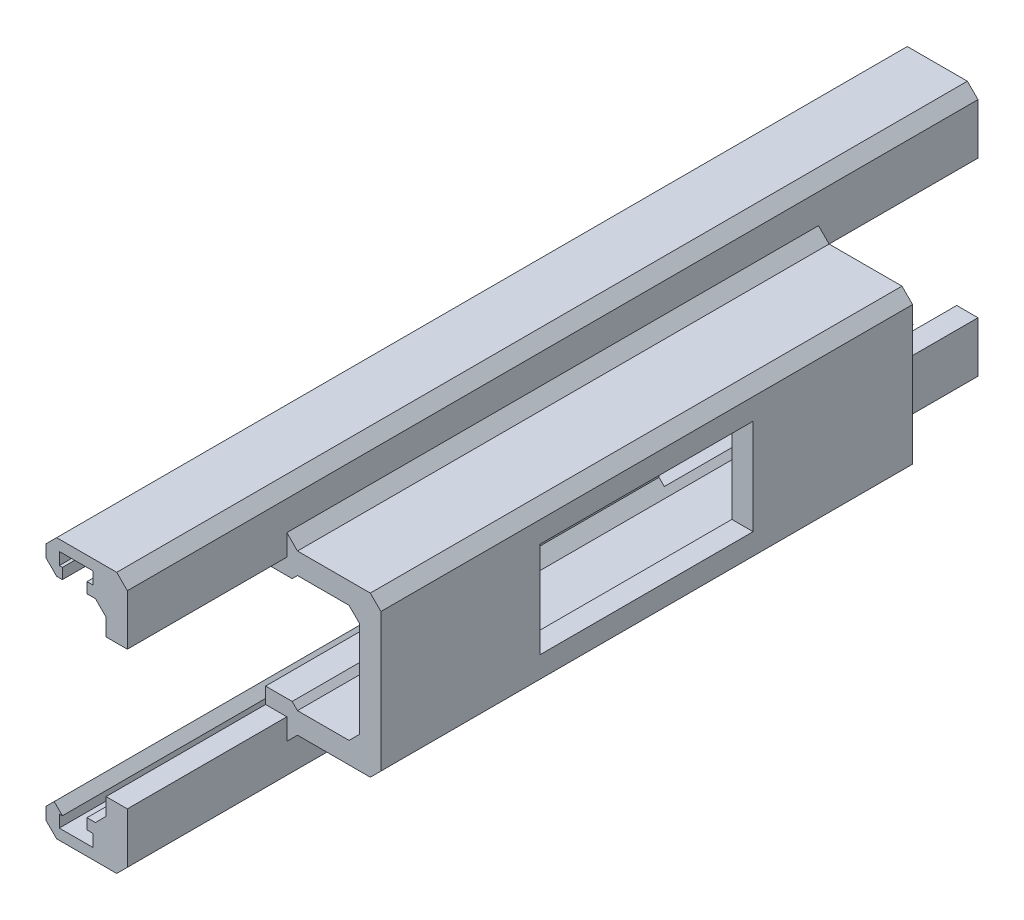
SolidWorks part; units mm, degrees
ref_plane "Plan de face" through (0, 0, 0) normal (0, 0, 1) x (1, 0, 0)
ref_plane "Plan de dessus" through (0, 0, 0) normal (0, 1, 0) x (1, 0, 0)
ref_plane "Plan de droite" through (0, 0, 0) normal (1, 0, 0) x (0, 0, -1)
sketch "Esquisse1" plane through (0, 0, 0) normal (0, 0, 1) x (1, 0, 0)
  line L0 (0, 1.9005) -> (0, -0.7738) construction
  line L2 (-2.5615, 1.0788) -> (-2.5615, -0.9212)
  line L3 (-1.9625, -2.4324) -> (-0.2921, -2.4324) construction
  line L4 (2.0615, 1.0788) -> (2.0615, -0.9212)
  line L5 (0.1295, 1.0788) -> (-0.2921, -2.4324) construction
  line L6 (-1.9625, -2.4324) -> (0.8705, 1.0788) construction
  line L7 (-3.15, -3.2212) -> (3.15, -3.2212)
  line L8 (-3.15, -3.2212) -> (-3.15, -0.9212)
  line L9 (-3.15, -0.9212) -> (-2.5615, -0.9212)
  line L10 (3.15, -3.2212) -> (3.15, -0.9212)
  line L11 (-3.15, -0.9212) -> (3.15, -3.2212) construction
  line L12 (2.0615, -0.9212) -> (3.15, -0.9212)
  line L13 (3.15, -0.9212) -> (-3.15, -3.2212) construction
  line L14 (0.1295, 1.0788) -> (0.8705, 1.0788) construction
  line L15 (-5.65, 1.0788) -> (-2.5615, 1.0788)
  line L16 (-5.65, 1.0788) -> (-5.65, -5.2212)
  line L17 (-5.65, -5.2212) -> (5.65, -5.2212)
  line L19 (-5.65, 1.0788) -> (5.65, -5.2212) construction
  line L20 (-5.65, -5.2212) -> (5.65, 1.0788) construction
  line L21 (2.0615, 1.0788) -> (5.65, 1.0788)
  line L22 (0, -0.2112) -> (0, 38.8288) construction
  line L23 (0, 19.3088) -> (-5.65, 19.3088) construction
  line L24 (-5.65, 43.8388) -> (5.65, 37.5388) construction
  line L25 (-5.65, 37.5388) -> (5.65, 43.8388) construction
  line L26 (3.15, 39.5388) -> (-3.15, 41.8388) construction
  line L27 (-3.15, 39.5388) -> (3.15, 41.8388) construction
  line L28 (-1.9625, 41.0501) -> (0.8705, 37.5388) construction
  line L29 (0.1295, 37.5388) -> (-0.2921, 41.0501) construction
  line L30 (0, 36.7172) -> (0, 39.3915) construction
  line L31 (2.0615, 37.5388) -> (5.65, 37.5388)
  line L33 (-5.65, 43.8388) -> (5.65, 43.8388)
  line L34 (-5.65, 37.5388) -> (-5.65, 43.8388)
  line L35 (-5.65, 37.5388) -> (-2.5615, 37.5388)
  line L36 (0.1295, 37.5388) -> (0.8705, 37.5388)
  line L37 (2.0615, 39.5388) -> (3.15, 39.5388)
  line L38 (3.15, 41.8388) -> (3.15, 39.5388)
  line L39 (-3.15, 39.5388) -> (-2.5615, 39.5388)
  line L40 (-3.15, 41.8388) -> (-3.15, 39.5388)
  line L41 (-3.15, 41.8388) -> (3.15, 41.8388)
  line L42 (2.0615, 37.5388) -> (2.0615, 39.5388)
  line L43 (-1.9625, 41.0501) -> (-0.2921, 41.0501)
  line L44 (-2.5615, 37.5388) -> (-2.5615, 39.5388)
  line L46 (5.65, 43.8388) -> (9.65, 43.8388)
  line L47 (5.65, 37.5388) -> (5.65, 1.0788)
  line L48 (5.65, -5.2212) -> (9.65, -5.2212)
  line L49 (9.65, 43.8388) -> (9.65, -5.2212)
  line L50 (5.65, -5.2212) -> (9.45, -5.2212)
  line L51 (5.65, 1.0788) -> (5.65, 37.5388)
  line L52 (5.65, 43.8388) -> (9.45, 43.8388)
  point P0 (0, 0)
  point P13 (0, -2.0712)
  point P43 (0, 40.6888)
  point P44 (0, 38.6177)
  dimension "D1" = 6.3
  dimension "D2" = 2.3
  dimension "D3" = 11.3
  dimension "D4" = 6.3
  dimension "D5" = 3.01
  dimension "D6" = 39.04
  dimension "D7" = 4
extrude "Boss.-Extru.1" add sketch "Esquisse1" along normal blind 80 and the other way blind 80 contours L21 L4 L12 L10 L7 L3 L8 L9 L2 L15 L16 L17 region at (-3.0754, 0.0788, 0)
sketch "Esquisse4" plane through (5.65, 0, 0) normal (-1, 0, 0) x (0, 0, 1)
  line L0 (-80, 37.5388) -> (80, 1.0788) construction
  line L1 (80, 37.5388) -> (-80, 1.0788) construction
  line L2 (-52.8674, 19.3088) -> (52.8674, 19.3088) construction
  line L3 (-16.5, 25.4088) -> (16.5, 25.4088) construction
  line L4 (-16.5, 25.4088) -> (-16.5, 13.2088) construction
  line L5 (-16.5, 13.2088) -> (16.5, 13.2088) construction
  line L6 (16.5, 25.4088) -> (16.5, 13.2088) construction
  line L7 (-16.5, 25.4088) -> (16.5, 13.2088) construction
  line L8 (-16.5, 13.2088) -> (16.5, 25.4088) construction
  line L9 (-11.5, 25.4088) -> (11.5, 25.4088)
  line L10 (-11.5, 25.4088) -> (-11.5, 13.2088)
  line L11 (-11.5, 13.2088) -> (11.5, 13.2088)
  line L12 (11.5, 25.4088) -> (11.5, 13.2088)
  line L13 (-11.5, 25.4088) -> (11.5, 13.2088) construction
  line L14 (-11.5, 13.2088) -> (11.5, 25.4088) construction
  line L15 (0, 25.4088) -> (0, 22.1174) construction
  circle A0 centre (-14, 19.3088) radius 1.5
  circle A1 centre (14, 19.3088) radius 1.5
  point P8 (0, 19.3088)
  point P13 (0, 19.3088)
  point P21 (0, 19.3088)
  point P23 (-11.5, 19.3088)
  dimension "D4" = 3
  dimension "D1" = 33
  dimension "D2" = 12.2
  dimension "D3" = 23
  dimension "D5" = 2.5
extrude "Enlèv. mat.-Extru.1" cut sketch "Esquisse4" against normal blind 95
sketch "Esquisse5" plane through (9.65, 0, 0) normal (1, 0, 0) x (0, 0, -1)
  line L0 (16.5, 25.4088) -> (16.5, 13.2088) construction
  line L1 (16.5, 13.2088) -> (-16.5, 13.2088) construction
  line L2 (16.5, 25.4088) -> (-16.5, 25.4088) construction
  line L3 (-16.5, 25.4088) -> (-16.5, 13.2088) construction
  line L4 (16.5, 25.4088) -> (16.5, 13.2088)
  line L5 (16.5, 13.2088) -> (11.5, 13.2088)
  line L6 (16.5, 25.4088) -> (11.5, 25.4088)
  line L7 (-16.5, 25.4088) -> (-16.5, 13.2088)
  line L8 (-11.5, 25.4088) -> (-11.5, 13.2088)
  line L9 (11.5, 25.4088) -> (11.5, 13.2088)
  line L10 (-11.5, 25.4088) -> (-16.5, 25.4088)
  line L11 (-11.5, 13.2088) -> (-16.5, 13.2088)
  circle A0 centre (-14, 19.3088) radius 1.5 construction
  circle A1 centre (14, 19.3088) radius 1.5 construction
  circle A2 centre (-14, 19.3088) radius 1.5
  circle A3 centre (14, 19.3088) radius 1.5
extrude "Enlèv. mat.-Extru.2" cut sketch "Esquisse5" against normal blind 2
sketch "Esquisse6" plane through (0, 0, 80) normal (0, 0, 1) x (1, 0, 0)
  line L0 (9.65, 19.3088) -> (23.35, 19.3088) construction
  line L1 (9.65, 43.8388) -> (9.65, -5.2212) construction
  line L3 (27.35, 34.3088) -> (27.35, 4.3088)
  line L4 (5.65, 37.5388) -> (5.65, 1.0788) construction
  line L6 (27.35, 34.3088) -> (9.65, 34.3088)
  line L7 (27.35, 34.3088) -> (27.35, 30.3088)
  line L8 (23.35, 30.3088) -> (9.65, 30.3088)
  line L9 (9.65, 34.3088) -> (9.65, 30.3088)
  line L11 (27.35, 30.3088) -> (27.35, 4.3088)
  line L12 (27.35, 4.3088) -> (23.35, 4.3088)
  line L13 (23.35, 30.3088) -> (23.35, 8.3088)
  line L14 (23.35, 8.3088) -> (9.65, 8.3088)
  line L15 (27.35, 8.3088) -> (27.35, 4.3088)
  line L16 (27.35, 4.3088) -> (9.65, 4.3088)
  line L17 (9.65, 8.3088) -> (9.65, 4.3088)
  point P6 (25.45, 19.3088)
  point P9 (27.35, 19.3088)
  dimension "D2" = 30
  dimension "D3" = 19.8
  dimension "D4" = 4
  dimension "D5" = 4
  dimension "D6" = 4
sketch "Esquisse9" plane through (0, 0, 0) normal (0, 0, 1) x (1, 0, 0)
  line L0 (27.35, 4.3088) -> (23.35, 4.3088) construction
  line L1 (27.35, 34.3088) -> (27.35, 4.3088) construction
  line L2 (27.35, 34.3088) -> (27.35, 30.3088) construction
  line L3 (27.35, 30.3088) -> (27.35, 4.3088) construction
  line L4 (27.35, 8.3088) -> (27.35, 4.3088) construction
  line L5 (27.35, 34.3088) -> (9.65, 34.3088) construction
  line L6 (9.65, 34.3088) -> (9.65, 30.3088) construction
  line L7 (23.35, 30.3088) -> (9.65, 30.3088) construction
  line L8 (23.35, 30.3088) -> (23.35, 8.3088) construction
  line L9 (23.35, 8.3088) -> (9.65, 8.3088) construction
  line L10 (9.65, 8.3088) -> (9.65, 4.3088) construction
  line L11 (27.35, 4.3088) -> (9.65, 4.3088) construction
  line L12 (27.35, 4.3088) -> (23.35, 4.3088)
  line L13 (27.35, 34.3088) -> (27.35, 4.3088)
  line L14 (27.35, 34.3088) -> (27.35, 30.3088)
  line L15 (27.35, 30.3088) -> (27.35, 4.3088)
  line L16 (27.35, 8.3088) -> (27.35, 4.3088)
  line L17 (27.35, 34.3088) -> (9.65, 34.3088)
  line L18 (9.65, 34.3088) -> (9.65, 30.3088)
  line L19 (23.35, 30.3088) -> (9.65, 30.3088)
  line L20 (23.35, 30.3088) -> (23.35, 8.3088)
  line L21 (23.35, 8.3088) -> (9.65, 8.3088)
  line L22 (9.65, 8.3088) -> (9.65, 4.3088)
  line L23 (27.35, 4.3088) -> (9.65, 4.3088)
extrude "Boss.-Extru.3" add sketch "Esquisse9" along normal blind 50 and the other way blind 50 contours L23 L12 L15 L13 L17 L18 L19 L20 L21 L22 region at (25.35, 4.6572, 0)
chamfer "Chanfrein2" distance 2 angle 45 17 edges at (-2.5615, 1.0788, 0) (23.35, 8.3088, 0) (23.35, 30.3088, 0) (9.65, 30.3088, 0) (5.65, 37.5388, 0) (5.65, 1.0788, 0) (-5.65, 1.0788, 0) (-5.65, -5.2212, 0) (9.65, -5.2212, 0) (9.65, 4.3088, 0) (27.35, 4.3088, 0) (27.35, 34.3088, 0) (9.65, 34.3088, 0) (9.65, 43.8388, 0) (-5.65, 37.5388, 0) (-5.65, 43.8388, 0) (9.65, 8.3088, 0)
sketch "Esquisse11" plane through (5.65, 0, 0) normal (-1, 0, 0) x (0, 0, 1)
  line L1 (50, 32.3088) -> (80, 32.3088)
  line L2 (50, 32.3088) -> (50, 6.3088)
  line L3 (50, 6.3088) -> (80, 6.3088)
  line L4 (50, 6.3088) -> (50, 32.3088)
  line L5 (-50, 6.3088) -> (50, 6.3088)
  line L6 (-50, 32.3088) -> (-50, 6.3088)
  line L7 (50, 32.3088) -> (-50, 32.3088)
  line L8 (50, 6.3088) -> (50, 32.3088)
  line L10 (-50, 32.3088) -> (-50, 6.3088)
  line L12 (80, 32.3088) -> (80, 6.3088)
  line L14 (-50, 32.3088) -> (-80, 32.3088)
  line L15 (-50, 32.3088) -> (-50, 6.3088)
  line L16 (-50, 6.3088) -> (-80, 6.3088)
  line L17 (-80, 32.3088) -> (-80, 6.3088)
  line L20 (-50, 19.3088) -> (50, 19.3088) construction
  line L21 (0, 32.3088) -> (0, 6.3088) construction
  line L22 (-20, 9.3088) -> (-50, 9.3088)
  line L23 (-20, 9.3088) -> (-20, 29.3088)
  line L24 (-20, 29.3088) -> (-50, 29.3088)
  line L25 (-50, 9.3088) -> (-50, 29.3088)
  line L26 (-20, 9.3088) -> (-50, 29.3088) construction
  line L27 (-20, 29.3088) -> (-50, 9.3088) construction
  line L28 (20, 29.3088) -> (50, 9.3088) construction
  line L29 (20, 9.3088) -> (50, 29.3088) construction
  line L30 (50, 9.3088) -> (50, 29.3088)
  line L31 (20, 29.3088) -> (50, 29.3088)
  line L32 (20, 9.3088) -> (20, 29.3088)
  line L33 (20, 9.3088) -> (50, 9.3088)
  line L34 (-80, 35.5388) -> (-80, 3.0788) construction
  line L35 (80, 35.5388) -> (80, 3.0788) construction
  point P6 (-35, 19.3088)
  point P26 (35, 19.3088)
  line M11 (80, 3.0788) -> (80, 35.5388)
  line M13 (-80, 35.5388) -> (-80, 3.0788)
  dimension "D4" = 30
  dimension "D5" = 20
  dimension "D1" = 0
extrude "Enlèv. mat.-Extru.4" cut sketch "Esquisse11" against normal blind 11 contours L16 L10 L14 M13 | L2 L3 L1 M11 | L23 L24 L15 L22 | L32 L33 L8 L31 region at (5.65, 19.3088, 65) region at (5.65, 19.3088, 35) region at (5.65, 19.3088, -65) region at (5.65, 19.3088, -35)
sketch "Esquisse12" plane through (27.35, 0, 0) normal (1, 0, 0) x (0, 0, -1)
  line L1 (10, 28.3088) -> (30, 28.3088)
  line L3 (10, 10.3088) -> (30, 10.3088)
  line L4 (50, 10.3088) -> (50, 28.3088)
  line L5 (-50, 10.3088) -> (50, 10.3088)
  line L6 (50, 10.3088) -> (50, 28.3088)
  line L7 (50, 28.3088) -> (-50, 28.3088)
  line L9 (-50, 10.3088) -> (50, 10.3088)
  line L11 (50, 28.3088) -> (-50, 28.3088)
  line L12 (30, 28.3088) -> (30, 10.3088)
  line L13 (-30, 28.3088) -> (-10, 28.3088)
  line L14 (-30, 28.3088) -> (-30, 10.3088)
  line L15 (-30, 10.3088) -> (-10, 10.3088)
  line L17 (50, 28.3088) -> (43.8886, 28.3088)
  line L18 (50, 28.3088) -> (50, 10.3088)
  line L19 (50, 10.3088) -> (43.8886, 10.3088)
  line L21 (-20.1228, 28.3088) -> (20, 28.3088)
  line L22 (-20.1228, 28.3088) -> (-20.1228, 10.3088)
  line L23 (-20.1228, 10.3088) -> (20, 10.3088)
  line L24 (20, 28.3088) -> (20, 10.3088)
  line L28 (-50, 28.3088) -> (-50, 10.3088)
  line L29 (-50, 28.3088) -> (-50, 10.3088)
  dimension "D3" = 20
  dimension "D6" = 20
  dimension "D1" = 0
extrude "Enlèv. mat.-Extru.5" cut sketch "Esquisse12" against normal blind 8 contours L24 L1 L11 L22 L15 L9 L3 region at (27.35, 19.3088, 0.0614)
